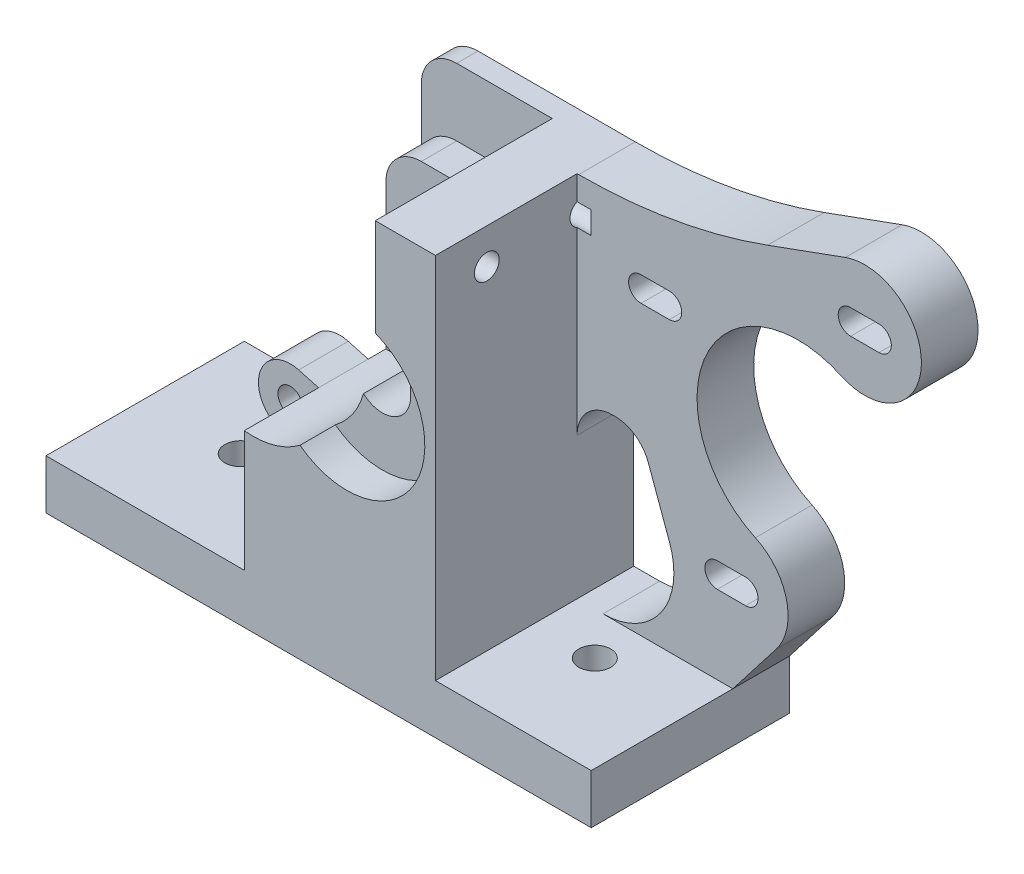
SolidWorks part; units mm, degrees
ref_plane "Front Plane" through (0, 0, 0) normal (0, 0, 1) x (1, 0, 0)
ref_plane "Top Plane" through (0, 0, 0) normal (0, 1, 0) x (1, 0, 0)
ref_plane "Right Plane" through (0, 0, 0) normal (1, 0, 0) x (0, 0, -1)
sketch "Sketch2" plane through (0, 0, 0) normal (0, 0, 1) x (1, 0, 0)
  line L0 (-39.5025, 0) -> (37.4975, 0) construction
  dimension "D1" = 77
sketch "Sketch4" plane through (0, 0, 0) normal (1, 0, 0) x (0, 0, -1)
  line L0 (0, 0) -> (0, 65) construction
  line L1 (0, 0) -> (-28, 0) construction
sketch "Sketch5" plane through (0, 0, 0) normal (0, 0, 1) x (1, 0, 0)
  line L0 (37.4975, 0) -> (-39.5025, 0)
  line L1 (-39.5025, 0) -> (-39.5025, 7)
  line L2 (-39.5025, 7) -> (-11.5, 7)
  line L3 (37.4975, 7) -> (37.4975, 0)
  line L4 (15.5, 7) -> (15.5, 32)
  line L5 (15.5, 32) -> (24.3525, 32)
  line L6 (24.3525, 32) -> (33.4518, 7)
  line L7 (56.1283, 60.187) -> (37.3016, 19.813) construction
  line L8 (-11.5, 7) -> (-11.5, 59)
  line L9 (-11.5, 59) -> (29.4767, 59)
  line L10 (29.4767, 59) -> (53.3922, 67.7045)
  line L11 (3, 0) -> (3, 59) construction
  line L12 (26.528, 49.4133) -> (37.3016, 19.813) construction
  line L13 (26.528, 49.4133) -> (56.1283, 60.187) construction
  line L14 (37.3016, 19.813) -> (66.902, 30.5867) construction
  line L15 (56.1283, 60.187) -> (66.902, 30.5867) construction
  line L16 (37.4975, 7) -> (43.6268, 14.9148)
  line L17 (15.5, 7) -> (33.4518, 7)
  circle A0 centre (3, 35) radius 11 construction
  circle A1 centre (3, 35) radius 4
  circle A2 centre (3, 35) radius 33 construction
  circle A3 centre (46.715, 40) radius 11 construction
  circle A4 centre (37.3016, 19.813) radius 1.75 construction
  circle A5 centre (26.528, 49.4133) radius 1.75 construction
  circle A6 centre (56.1283, 60.187) radius 1.75 construction
  circle A7 centre (66.902, 30.5867) radius 1.75 construction
  arc A8 (52.7474, 52.9365) -> (53.3922, 67.7045) centre (56.1283, 60.187) ccw
  arc A9 (45.3016, 19.813) -> (40.6826, 27.0635) centre (37.3016, 19.813) ccw
  arc A10 (45.3016, 19.813) -> (43.6268, 14.9148) centre (37.3016, 19.813) cw
  arc A11 (52.7474, 52.9365) -> (40.6826, 27.0635) centre (46.715, 40) ccw
  dimension "D1" = 22
  dimension "D7" = 8
  dimension "D10" = 22
  dimension "D11" = 66
  dimension "D14" = 3.5
  dimension "D15" = 8
  dimension "D5" = 33
  dimension "D2" = 7
  dimension "D3" = 27
  dimension "D4" = 25
  dimension "D6" = 31.5
  dimension "D8" = 52
  dimension "D9" = 14.5
  dimension "D12" = 28
  dimension "D13" = 70
  dimension "D16" = 3
extrude "Boss-Extrude1" add sketch "Sketch5" along normal blind 8 contours A11 A8 L10 L9 L8 L2 L1 L0 L3 L17 L4 L5 L6 A9 A1 region at (14.232, 31.6574, 0)
sketch "Sketch6" plane through (0, 0, 8) normal (0, 0, 1) x (1, 0, 0)
  line L0 (37.4975, 0) -> (-39.5025, 0) construction
  line L1 (-39.5025, 0) -> (-39.5025, 7) construction
  line L2 (-39.5025, 7) -> (-11.5, 7) construction
  line L3 (-11.5, 7) -> (-11.5, 59) construction
  line L4 (37.4975, 0) -> (-39.5025, 0)
  line L5 (-39.5025, 0) -> (-39.5025, 7)
  line L6 (-39.5025, 7) -> (-11.5, 7)
  line L7 (-11.5, 7) -> (-11.5, 59)
  line L8 (37.4975, 0) -> (37.4975, 7)
  line L9 (37.4975, 7) -> (15.5, 7)
  line L10 (15.5, 7) -> (15.5, 59)
  line L11 (-11.5, 59) -> (29.4767, 59) construction
  line L12 (15.5, 59) -> (-11.5, 59)
  line L13 (37.4975, 7) -> (37.4975, 0) construction
  circle A0 centre (3, 35) radius 4 construction
  circle A1 centre (3, 35) radius 4
extrude "Boss-Extrude2" add sketch "Sketch6" along normal blind 20
sketch "Sketch7" plane through (0, 0, 0) normal (0, -1, 0) x (1, 0, 0)
  line L0 (37.4975, 28) -> (-39.5025, 0) construction
  line L1 (-39.5025, 28) -> (37.4975, 0) construction
  circle A0 centre (-1.0025, 14) radius 7.875
  dimension "D1" = 15.75
extrude "Cut-Extrude1" cut sketch "Sketch7" against normal blind 4
ref_axis "Axis1" through (-1.0025, 4, 14) along (0, -1, 0)
sketch "Sketch8" plane through (0, 59, 0) normal (0, 1, 0) x (1, 0, 0)
  circle A0 centre (-1.0025, -14) radius 1.75
  dimension "D1" = 3.5
extrude "Cut-Extrude2" cut sketch "Sketch8" against normal blind 64
sketch "Sketch9" plane through (0, 0, 0) normal (0, -1, 0) x (1, 0, 0)
  line L0 (37.4975, 14) -> (-39.5025, 14) construction
  line L1 (37.4975, 28) -> (37.4975, 0) construction
  line L2 (-39.5025, 28) -> (-39.5025, 0) construction
  circle A0 centre (23.9975, 14) radius 2.25
  circle A1 centre (-26.0025, 14) radius 2.25
  dimension "D1" = 4.5
  dimension "D2" = 50
  dimension "D3" = 13.5
extrude "Cut-Extrude3" cut sketch "Sketch9" against normal blind 64
fillet "Fillet1" radius 10 1 edges
fillet "Fillet2" radius 78 1 edges at (29.4767, 59, 4)
fillet "Fillet3" radius 5 1 edges
sketch "Sketch10" plane through (0, 0, 0) normal (0, 0, -1) x (-1, 0, 0)
  circle A0 centre (-3, 35) radius 11
  dimension "D1" = 22
extrude "Cut-Extrude4" cut sketch "Sketch10" against normal blind 5
sketch "Sketch11" plane through (0, 0, 28) normal (0, 0, 1) x (1, 0, 0)
  circle A0 centre (3, 35) radius 11
  circle A1 centre (3, 35) radius 11 construction
extrude "Cut-Extrude5" cut sketch "Sketch11" against normal blind 5
sketch "Sketch13" plane through (-11.5, 0, 0) normal (-1, 0, 0) x (0, 0, 1)
  line L1 (14, 4) -> (14, 59) construction
  line L2 (28, 59) -> (0, 59) construction
  circle A0 centre (20.75, 54) radius 1.75
  circle A1 centre (7.25, 54) radius 1.75
  dimension "D1" = 3.5
  dimension "D3" = 6.75
  dimension "D2" = 6.75
  dimension "D4" = 5
extrude "Cut-Extrude7" cut sketch "Sketch13" against normal blind 29
fillet "Fillet4" radius 5 1 edges at (24.3525, 32, 4)
sketch "Sketch14" plane through (0, 0, 8) normal (0, 0, 1) x (1, 0, 0)
  line L0 (58.1283, 60.187) -> (54.1283, 60.187) construction
  line L1 (58.1283, 58.437) -> (54.1283, 58.437)
  line L2 (58.1283, 61.937) -> (54.1283, 61.937)
  line L3 (39.3016, 19.813) -> (35.3016, 19.813) construction
  line L4 (39.3016, 18.063) -> (35.3016, 18.063)
  line L5 (39.3016, 21.563) -> (35.3016, 21.563)
  line L6 (28.528, 49.4133) -> (24.528, 49.4133) construction
  line L7 (28.528, 47.6633) -> (24.528, 47.6633)
  line L8 (28.528, 51.1633) -> (24.528, 51.1633)
  circle A0 centre (56.1283, 60.187) radius 1.75 construction
  circle A1 centre (26.528, 49.4133) radius 1.75 construction
  circle A2 centre (37.3016, 19.813) radius 1.75 construction
  circle A3 centre (56.1283, 60.187) radius 1.75 construction
  circle A4 centre (26.528, 49.4133) radius 1.75 construction
  circle A5 centre (37.3016, 19.813) radius 1.75 construction
  arc A6 (58.1283, 58.437) -> (58.1283, 61.937) centre (58.1283, 60.187) ccw
  arc A7 (54.1283, 61.937) -> (54.1283, 58.437) centre (54.1283, 60.187) ccw
  arc A8 (39.3016, 18.063) -> (39.3016, 21.563) centre (39.3016, 19.813) ccw
  arc A9 (35.3016, 21.563) -> (35.3016, 18.063) centre (35.3016, 19.813) ccw
  arc A10 (28.528, 47.6633) -> (28.528, 51.1633) centre (28.528, 49.4133) ccw
  arc A11 (24.528, 51.1633) -> (24.528, 47.6633) centre (24.528, 49.4133) ccw
  point P11 (56.1283, 60.187)
  point P18 (37.3016, 19.813)
  point P23 (26.528, 49.4133)
  dimension "D1" = 1.75
  dimension "D2" = 4
extrude "Cut-Extrude8" cut sketch "Sketch14" against normal blind 29
sketch "Sketch15" plane through (0, 0, 0) normal (0, 0, -1) x (-1, 0, 0)
  line L4 (-39.3016, 16.063) -> (-35.3016, 16.063)
  line L5 (-35.3016, 23.563) -> (-39.3016, 23.563)
  line L6 (-39.3016, 16.063) -> (-35.3016, 16.063)
  line L7 (-35.3016, 23.563) -> (-39.3016, 23.563)
  line L10 (-24.528, 53.1633) -> (-28.528, 53.1633)
  line L11 (-28.528, 45.6633) -> (-24.528, 45.6633)
  line L12 (-24.528, 53.1633) -> (-28.528, 53.1633)
  line L13 (-28.528, 45.6633) -> (-24.528, 45.6633)
  line L16 (-54.1283, 63.937) -> (-58.1283, 63.937)
  line L17 (-58.1283, 56.437) -> (-54.1283, 56.437)
  line L18 (-54.1283, 63.937) -> (-58.1283, 63.937)
  line L19 (-58.1283, 56.437) -> (-54.1283, 56.437)
  arc A4 (-39.3016, 23.563) -> (-39.3016, 16.063) centre (-39.3016, 19.813) ccw
  arc A5 (-35.3016, 16.063) -> (-35.3016, 23.563) centre (-35.3016, 19.813) ccw
  arc A6 (-39.3016, 23.563) -> (-39.3016, 16.063) centre (-39.3016, 19.813) ccw
  arc A7 (-35.3016, 16.063) -> (-35.3016, 23.563) centre (-35.3016, 19.813) ccw
  arc A10 (-24.528, 45.6633) -> (-24.528, 53.1633) centre (-24.528, 49.4133) ccw
  arc A11 (-28.528, 53.1633) -> (-28.528, 45.6633) centre (-28.528, 49.4133) ccw
  arc A12 (-24.528, 45.6633) -> (-24.528, 53.1633) centre (-24.528, 49.4133) ccw
  arc A13 (-28.528, 53.1633) -> (-28.528, 45.6633) centre (-28.528, 49.4133) ccw
  arc A16 (-54.1283, 56.437) -> (-54.1283, 63.937) centre (-54.1283, 60.187) ccw
  arc A17 (-58.1283, 63.937) -> (-58.1283, 56.437) centre (-58.1283, 60.187) ccw
  arc A18 (-54.1283, 56.437) -> (-54.1283, 63.937) centre (-54.1283, 60.187) ccw
  arc A19 (-58.1283, 63.937) -> (-58.1283, 56.437) centre (-58.1283, 60.187) ccw
  dimension "D1" = 2
  dimension "D2" = 2
  dimension "D3" = 2
extrude "Cut-Extrude9" cut sketch "Sketch15" against normal blind 3
sketch "Sketch18" plane through (0, 0, 28) normal (0, 0, 1) x (1, 0, 0)
  line L0 (3, 35) -> (-10.2525, 35) construction
  line L8 (0.7475, 38.3055) -> (0.7475, 59) construction
  circle A0 centre (-10.2525, 35) radius 11
  dimension "D1" = 22
extrude "Cut-Extrude10" cut sketch "Sketch18" against normal up to surface (20 mm away) up to face at (26.528, 49.4133, 8)
ref_plane "Plane1" through (0, 0, 14) normal (0, 0, 1) x (1, 0, 0)
sketch "Sketch19" plane through (0, 0, 14) normal (0, 0, 1) x (1, 0, 0)
  line L0 (-18.5977, 17.2359) -> (-11.5, 10.5)
  line L1 (-11.5, 24.071) -> (-11.5, 7) construction
  line L2 (-14.3124, 24.8405) -> (-11.5, 24.071)
  line L3 (-11.5, 24.071) -> (-11.5, 10.5)
  line L4 (3, 35) -> (-20.2488, 35) construction
  circle A0 centre (-15.5, 20.5) radius 1.75
  arc A1 (-14.3124, 24.8405) -> (-18.5977, 17.2359) centre (-15.5, 20.5) ccw
  dimension "D1" = 3.5
  dimension "D2" = 3.5
  dimension "D3" = 4.5
  dimension "D4" = 4
  dimension "D5" = 14.5
extrude "Boss-Extrude3" add sketch "Sketch19" along normal blind 3.5 and the other way blind 3.5
sketch "Sketch20" plane through (0, 0, 28) normal (0, 0, 1) x (1, 0, 0)
  line L1 (-11.5, 59) -> (7, 59)
  line L2 (-11.5, 59) -> (-11.5, 35)
  line L3 (-11.5, 35) -> (7, 35)
  line L4 (7, 59) -> (7, 35)
  arc A0 (0.3353, 32.0168) -> (0.3353, 37.9832) centre (3, 35) ccw construction
extrude "Cut-Extrude11" cut sketch "Sketch20" against normal up to surface (20 mm away) up to face at (-5.1855, 35, 8)
sketch "Sketch21" plane through (0, 0, 8) normal (0, 0, 1) x (1, 0, 0)
  line L0 (7, 45.247) -> (7, 59) construction
  line L1 (-11.5, 59) -> (7, 59)
  line L2 (-11.5, 59) -> (-11.5, 49.5)
  line L3 (-11.5, 49.5) -> (7, 49.5)
  line L4 (7, 59) -> (7, 49.5)
  circle A1 centre (3, 35) radius 11 construction
  dimension "D1" = 3.5
extrude "Cut-Extrude12" cut sketch "Sketch21" against normal blind 5
fillet "Fillet5" radius 5 2 edges at (-11.5, 49.5, 5.5) (-11.5, 59, 1.5)
ref_axis "Axis2" through (-15.5, 20.5, 10.5) along (0, 0, 1)
ref_plane "Plane2" through (0, 20.5, 0) normal (0, -1, 0) x (-1, 0, 0)
equation "\"D3@Sketch9\"=(77-50)/2"
